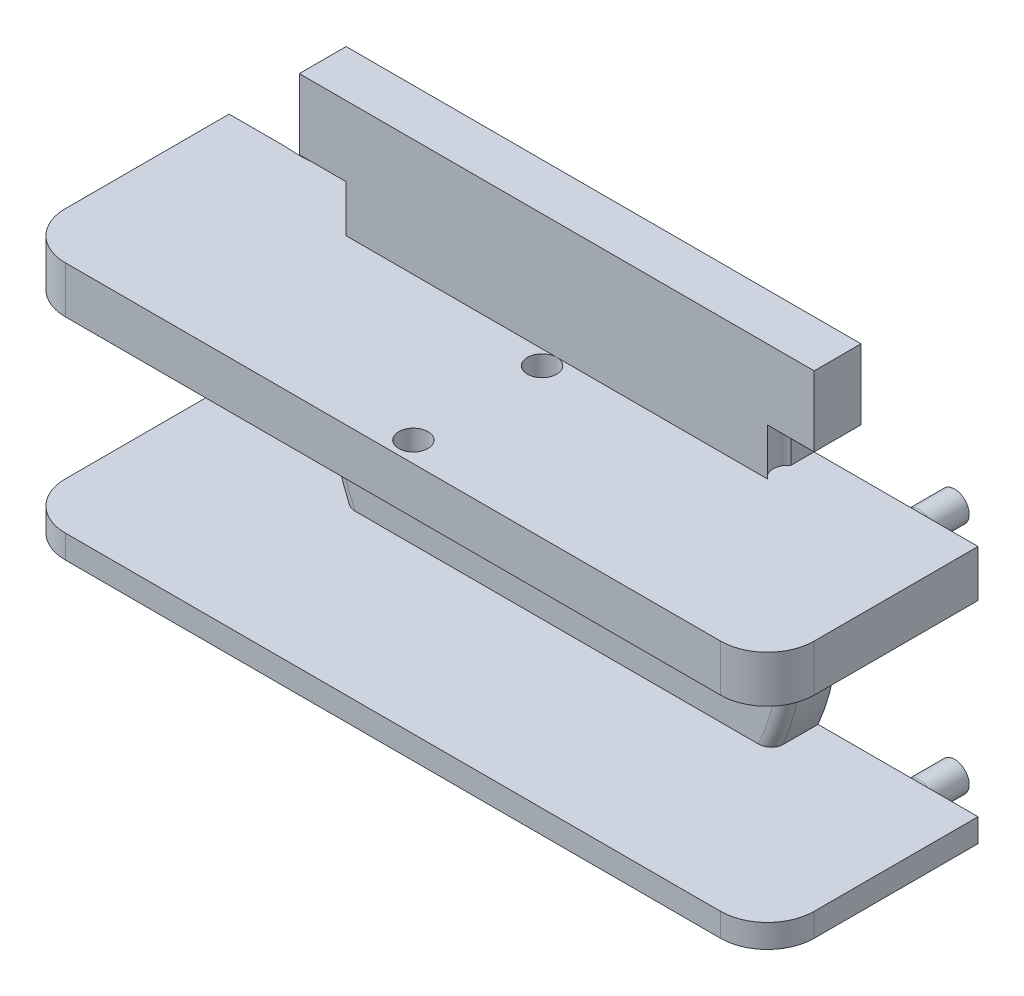
SolidWorks part; units mm, degrees
material "UNOBTANIUM"
ref_plane "Top Plane" through (0, 0, 0) normal (0, 0, 1) x (1, 0, 0)
ref_plane "Right Plane" through (0, 0, 0) normal (0, 1, 0) x (1, 0, 0)
ref_plane "Front Plane" through (0, 0, 0) normal (1, 0, 0) x (0, 0, -1)
ref_axis "x-axis" through (-17.6, 0, 0) along (1, 0, 0)
ref_axis "y-axis" through (0, -9.7375, 0) along (0, 1, 0)
ref_axis "z-axis" through (0, 0, 8.775) along (0, 0, -1)
sketch "Sketch1" plane through (0, 0, 0) normal (0, 0, 1) x (1, 0, 0)
  line L0 (-11, 6) -> (-11, 11)
  line L1 (-11, -6) -> (11, -6)
  line L2 (-11, -6) -> (-11, 6)
  line L3 (-11, 6) -> (11, 6) construction
  line L4 (11, -6) -> (11, 6)
  line L5 (-11, -6) -> (11, 6) construction
  line L6 (-11, 6) -> (11, -6) construction
  line L7 (-11, 11) -> (11, 11)
  line L8 (11, 11) -> (11, 6)
  circle A0 centre (0, 0) radius 9.25 construction
  point P0 (0, 0)
  dimension "D1" = 18.5
  dimension "D2" = 22
  dimension "D3" = 12
  dimension "D4" = 5
extrude "Boss-Extrude1" add sketch "Sketch1" along normal blind 2
sketch "Sketch2" plane through (0, 0, 2) normal (0, 0, -1) x (-1, 0, 0)
  circle A0 centre (0, 0) radius 1.575
  dimension "D1" = 3.15
extrude "Boss-Extrude2" add sketch "Sketch2" along normal blind 4 separate body
sketch "Sketch3" plane through (0, 0, 0) normal (0, 0, -1) x (-1, 0, 0)
  line L0 (11, -6) -> (-11, 6) construction
  circle A0 centre (0, 0) radius 1.8
  dimension "D1" = 3.6
extrude "Boss-Extrude3" add sketch "Sketch3" along normal blind 0.85
sketch "Sketch4" plane through (0, 0, 0) normal (0, 0, -1) x (-1, 0, 0)
  line L0 (11, -6) -> (-11, -6) construction
  line L1 (11, 11) -> (9, 11)
  line L2 (11, 11) -> (11, -6)
  line L3 (11, -6) -> (9, -6)
  line L4 (9, 11) -> (9, -6)
  line L5 (0, -6) -> (0, 11) construction
  line L7 (-9, 11) -> (-9, -6)
  line L8 (-11, -6) -> (-9, -6)
  line L9 (-11, 11) -> (-11, -6)
  line L10 (-11, 11) -> (-9, 11)
  line L11 (11, 11) -> (-11, 11) construction
  dimension "D1" = 2
extrude "Boss-Extrude4" add sketch "Sketch4" along normal blind 0.001
sketch "Sketch5" plane through (0, 0, 0) normal (0, 0, -1) x (-1, 0, 0)
  line L0 (-9, -6) -> (-9, 11) construction
  line L1 (9, 11) -> (-9, 11)
  line L2 (9, 11) -> (9, 9)
  line L3 (9, 9) -> (-9, 9)
  line L4 (-9, 11) -> (-9, 9)
  dimension "D1" = 2
extrude "Boss-Extrude5" add sketch "Sketch5" along normal up to surface (0.001 mm away) up to face at (-10, 2.5, -0.001)
sketch "Sketch6" plane through (11, 0, 0) normal (1, 0, 0) x (0, 0, -1)
  line L0 (-2, -6) -> (-2, 11) construction
  line L1 (0.001, -6) -> (-2, -6)
  line L2 (0.001, -6) -> (0.001, -4)
  line L3 (0.001, -4) -> (-2, -4)
  line L4 (-2, -6) -> (-2, -4)
  line L6 (0.001, 11) -> (0.001, -6) construction
  line L7 (-2, 6) -> (0.001, 6)
  line L8 (-2, 6) -> (-2, 4)
  line L9 (-2, 4) -> (0.001, 4)
  line L10 (0.001, 6) -> (0.001, 4)
  dimension "D1" = 2
extrude "Boss-Extrude6" add sketch "Sketch6" along normal blind 5
mirror "Mirror1" about plane through (0, 0, 0) normal (1, 0, 0) of "Boss-Extrude6"
sketch "Sketch7" plane through (0, 0, -0.001) normal (0, 0, -1) x (-1, 0, 0)
  line L0 (-9, -6) -> (-9, 9) construction
  line L1 (-9, 0) -> (-9, 9)
  line L2 (-9, 9) -> (0, 9)
  line L3 (-9, 0) -> (-9, -6)
  line L4 (-9, -6) -> (-6.7082, -6)
  line L5 (11, -6) -> (-11, -6) construction
  arc A0 (0, 9) -> (-6.7082, -6) centre (0, 0) ccw
  line M18 (-9, -6) -> (-9, 9)
  line M19 (-9, 9) -> (9, 9)
extrude "Boss-Extrude7" add sketch "Sketch7" against normal up to surface (0.001 mm away) contours A0 L4 M18 | A0 M19 M18 region at (8.3306, -4.5409, -0.001) region at (6.9897, 6.9897, -0.001) up to face at (1.8, 0, 0)
sketch "Sketch8" plane through (0, 0, -0.001) normal (0, 0, -1) x (-1, 0, 0)
  line L0 (-11, 4) -> (-9.1652, 4)
  line L1 (-11, 4) -> (-11, -4)
  line L2 (-11, -4) -> (-9.1652, -4)
  arc A1 (-9.1652, 4) -> (-9.1652, -4) centre (0, 0) ccw
  dimension "D1" = 10
extrude "Cut-Extrude1" cut sketch "Sketch8" against normal through all
sketch "Sketch9" plane through (0, 0, -0.001) normal (0, 0, -1) x (-1, 0, 0)
  line L0 (-16, -4) -> (-9.1652, -4) construction
  line L1 (-8.0623, 4) -> (-11, 4)
  line L2 (-8.0623, 4) -> (-8.0623, -4)
  line L3 (-8.0623, -4) -> (-11, -4)
  line L4 (-11, 4) -> (-11, -4)
  line L5 (-11, -6) -> (-11, 6) construction
  arc A0 (0, 9) -> (-6.7082, -6) centre (0, 0) ccw construction
  arc A1 (0, 9) -> (-6.7082, -6) centre (0, 0) ccw construction
extrude "Cut-Extrude2" cut sketch "Sketch9" against normal up to surface (0.001 mm away) up to face at (1.8, 0, 0)
mirror "Mirror2" about plane through (0, 0, 0) normal (1, 0, 0) of "Cut-Extrude2", "Boss-Extrude7", "Cut-Extrude1"
sketch "Sketch21" plane through (0, 0, -0.001) normal (0, 0, -1) x (-1, 0, 0)
  circle A0 centre (0, 0) radius 9.75
  circle A1 centre (0, 0) radius 9 construction
  circle A2 centre (0, 0) radius 1.8 construction
  circle A3 centre (0, 0) radius 1.8
  dimension "D1" = 0.75
extrude "Cut-Extrude11" cut sketch "Sketch21" against normal up to surface (0.001 mm away) up to face at (0, -0.7091, 0)
sketch "Sketch10" plane through (0, 0, 2) normal (0, 0, 1) x (1, 0, 0)
  line L0 (-16, -4) -> (-16, -6) construction
  line L1 (16, -6) -> (-16, -6)
  line L2 (16, -6) -> (16, -4)
  line L3 (16, -4) -> (-16, -4)
  line L4 (-16, -6) -> (-16, -4)
  line L5 (-16, -4) -> (-9.1652, -4) construction
  line L7 (-16, 6) -> (16, 6)
  line L8 (-16, 6) -> (-16, 4)
  line L9 (-16, 4) -> (16, 4)
  line L10 (16, 6) -> (16, 4)
extrude "Boss-Extrude8" add sketch "Sketch10" along normal blind 7
fillet "Fillet1" radius 0.5 2 edges at (10, 0, 2) (-10, 0, 2)
sketch "Sketch11" plane through (0, 0, -0.001) normal (0, 0, -1) x (-1, 0, 0)
  line L0 (-16, -5) -> (-13, -5) construction
  line L1 (-16, -6) -> (-16, -4) construction
  circle A0 centre (-13, -5) radius 0.625
  dimension "D1" = 1.25
  dimension "D2" = 3
extrude "Boss-Extrude9" add sketch "Sketch11" along normal blind 2
sketch "Sketch14" plane through (0, 0, -0.001) normal (0, 0, -1) x (-1, 0, 0)
  line L1 (11, 6) -> (9, 6)
  line L2 (11, 6) -> (11, 8)
  line L3 (11, 8) -> (9, 8)
  line L4 (9, 6) -> (9, 8)
  line L5 (-11, 6) -> (-9, 6)
  line L6 (-11, 6) -> (-11, 8)
  line L7 (-11, 8) -> (-9, 8)
  line L8 (-9, 6) -> (-9, 8)
  dimension "D1" = 18
  dimension "D2" = 2
extrude "Cut-Extrude5" cut sketch "Sketch14" against normal through all
sketch "Sketch12" plane through (0, 0, -0.001) normal (0, 0, -1) x (-1, 0, 0)
  line L0 (-16, -5) -> (-13, -5) construction
  line L1 (-16, -6) -> (-16, -4) construction
  line L3 (16, -5) -> (13, -5) construction
  line L4 (16, -6) -> (16, -4) construction
  circle A0 centre (13, -5) radius 0.675
  circle A1 centre (-13, -5) radius 0.625 construction
  circle A2 centre (-13, -5) radius 0.625 construction
  dimension "D1" = 1.35
  dimension "D2" = 1.25
extrude "Cut-Extrude3" cut sketch "Sketch12" against normal blind 2.5
sketch "Sketch16" plane through (0, 6, 0) normal (0, 1, 0) x (1, 0, 0)
  line L0 (-9, -2) -> (-9, 0.001) construction
  line L1 (-9, -1) -> (-9, -2)
  arc A1 (-9, -1) -> (-9, -2) centre (-9.375, -1.5) cw
  dimension "D1" = 0.25
  dimension "D2" = 1
extrude "Cut-Extrude6" cut sketch "Sketch16" along normal blind 2
mirror "Mirror3" about plane through (0, 0, 0) normal (0, 1, 0) of "Boss-Extrude9", "Cut-Extrude3"
mirror "Mirror4" about plane through (0, 0, 0) normal (1, 0, 0) of "Cut-Extrude6"
fillet "Fillet2" radius 0.5 2 edges at (12.375, 5, -0.001) (13.625, -5, -0.001)
fillet "Fillet3" radius 0.5 2 edges at (-13.675, 5, -0.001) (-13.675, -5, -0.001)
fillet "Fillet4" radius 2 4 edges at (16, -5, 9) (16, 5, 9) (-16, -5, 9) (-16, 5, 9)
sketch "Sketch17" plane through (0, -6, 0) normal (0, -1, 0) x (1, 0, 0)
  line L0 (-16, 7) -> (-16, -0.001) construction
  line L1 (-14, 9) -> (14, 9) construction
  line L2 (16, 7) -> (16, -0.001) construction
  line L3 (-16, 7) -> (-16, -0.001)
  line L4 (-14, 9) -> (14, 9)
  line L5 (16, 7) -> (16, -0.001)
  line L6 (14.5, 7) -> (14.5, -0.001)
  line L8 (-14, 7.5) -> (14, 7.5)
  line L9 (-14.5, 7) -> (-14.5, -0.001)
  line L10 (14.5, -0.001) -> (16, -0.001)
  line L11 (-14.5, -0.001) -> (-16, -0.001)
  arc A0 (-14, 9) -> (-16, 7) centre (-14, 7) ccw construction
  arc A1 (16, 7) -> (14, 9) centre (14, 7) ccw construction
  arc A2 (-14, 9) -> (-16, 7) centre (-14, 7) ccw
  arc A3 (16, 7) -> (14, 9) centre (14, 7) ccw
  arc A4 (14.5, 7) -> (14, 7.5) centre (14, 7) ccw
  arc A5 (-14, 7.5) -> (-14.5, 7) centre (-14, 7) ccw
  dimension "D1" = 1.5
extrude "Cut-Extrude7" cut sketch "Sketch17" against normal blind 1 and the other way through all
sketch "Sketch19" plane through (0, 6, 0) normal (0, 1, 0) x (1, 0, 0)
  line L0 (9, -2) -> (-9, -2) construction
  line L1 (0, -2.625) -> (0, -2) construction
  line L2 (9, -2) -> (-9, -2) construction
  circle A0 centre (0, -2.625) radius 0.625
  circle A1 centre (0, -8.125) radius 0.625
  point P4 (0, -2)
  dimension "D1" = 1.25
  dimension "D2" = 5.5
extrude "Cut-Extrude9" cut sketch "Sketch19" against normal up to surface (2 mm away) up to face at (0.0154, 4, 1.9997)
sketch "Sketch20" plane through (0, 0, -0.001) normal (0, 0, -1) x (-1, 0, 0)
  line L0 (-9, 8) -> (-11, 8) construction
  line L1 (-11, 11) -> (-9, 11)
  line L2 (-11, 11) -> (-11, 8)
  line L3 (-11, 8) -> (-9, 8)
  line L4 (-9, 11) -> (-9, 8)
  line L5 (11, 11) -> (-11, 11) construction
  line L6 (11, 8) -> (9, 8)
  line L7 (11, 8) -> (11, 11)
  line L8 (11, 11) -> (9, 11)
  line L9 (9, 8) -> (9, 11)
  dimension "D1" = 2
combine bodies "Combine2" operation type subtract main body 122 bodies to subtract 102
equation "\"D1@Sketch12\"=\"D2@Sketch12\"+.1"
